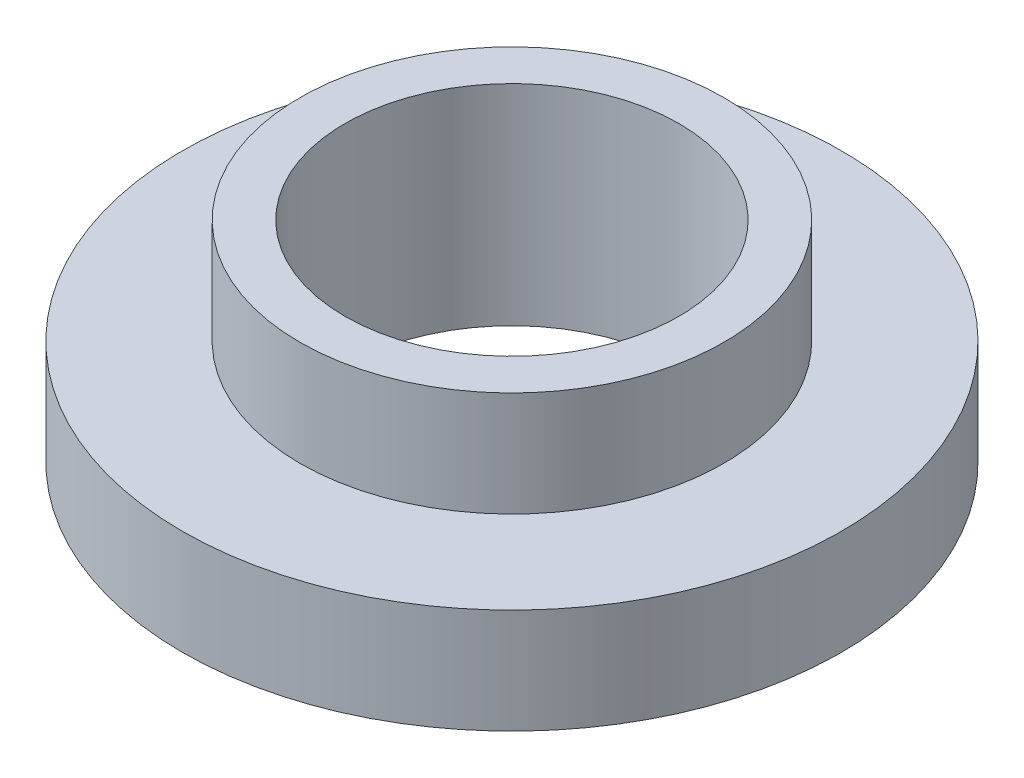
SolidWorks part; units mm, degrees
ref_plane "Front Plane" through (0, 0, 0) normal (0, 0, 1) x (1, 0, 0)
ref_plane "Top Plane" through (0, 0, 0) normal (0, 1, 0) x (1, 0, 0)
ref_plane "Right Plane" through (0, 0, 0) normal (1, 0, 0) x (0, 0, -1)
sketch "Sketch1" plane through (0, 0, 0) normal (0, 1, 0) x (1, 0, 0)
  circle A0 centre (0, 0) radius 11.15
  circle A1 centre (0, 0) radius 22
extrude "Boss-Extrude1" add sketch "Sketch1" along normal blind 7
sketch "Sketch2" plane through (0, 7, 0) normal (0, 1, 0) x (1, 0, 0)
  circle A0 centre (0, 0) radius 11.15
  circle A1 centre (0, 0) radius 14.15
extrude "Boss-Extrude2" add sketch "Sketch2" along normal blind 7
